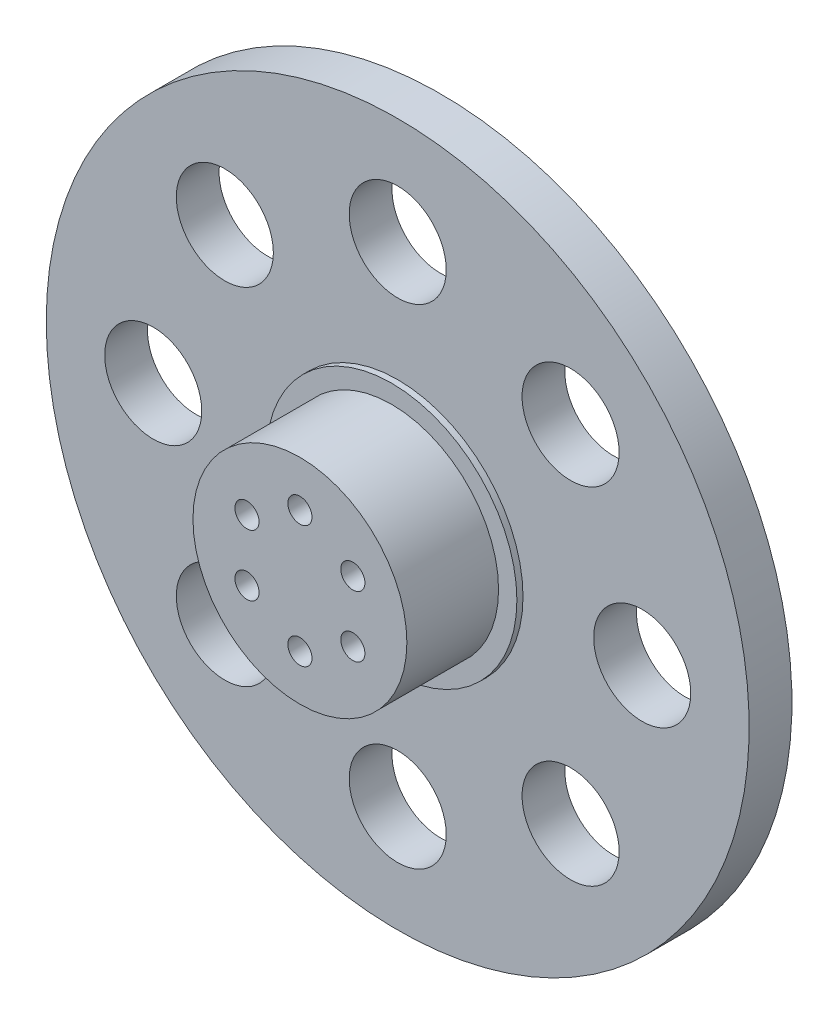
SolidWorks part; units mm, degrees
ref_plane "Front Plane" through (0, 0, 0) normal (0, 0, 1) x (1, 0, 0)
ref_plane "Top Plane" through (0, 0, 0) normal (0, 1, 0) x (1, 0, 0)
ref_plane "Right Plane" through (0, 0, 0) normal (1, 0, 0) x (0, 0, -1)
sketch "Sketch1" plane through (0, 0, 0) normal (0, 0, 1) x (1, 0, 0)
  circle A0 centre (0, 0) radius 17.5
  dimension "D1" = 35
extrude "Boss-Extrude1" add sketch "Sketch1" along normal blind 15
sketch "Sketch7" plane through (0, 0, 0) normal (0, 0, -1) x (-1, 0, 0)
  circle A0 centre (0, 0) radius 20.5
  dimension "D1" = 41
extrude "Boss-Extrude3" add sketch "Sketch7" along normal blind 1
sketch "Sketch3" plane through (0, 0, -1) normal (0, 0, -1) x (-1, 0, 0)
  circle A0 centre (0, 0) radius 57.5
  dimension "D1" = 115
extrude "Boss-Extrude2" add sketch "Sketch3" along normal blind 7
sketch "Sketch4" plane through (0, 0, -8) normal (0, 0, -1) x (-1, 0, 0)
  circle A0 centre (0, 0) radius 11
  dimension "D1" = 22
extrude "Cut-Extrude1" cut sketch "Sketch4" against normal blind 7
sketch "Sketch5" plane through (0, 0, -1) normal (0, 0, -1) x (-1, 0, 0)
  circle A0 centre (0, 0) radius 7.5
  dimension "D1" = 15
extrude "Cut-Extrude2" cut sketch "Sketch5" against normal blind 0.5
sketch "Sketch6" plane through (0, 0, 15) normal (0, 0, 1) x (1, 0, 0)
  circle A0 centre (0, 10) radius 1.975
  dimension "D1" = 3.95
  dimension "D2" = 10
extrude "Cut-Extrude3" cut sketch "Sketch6" against normal blind 6
pattern_circular "CirPattern1" count 6 over 360 about axis through (0, 0, 15) along (0, 0, 1) of "Cut-Extrude3"
sketch "Sketch8" plane through (0, 0, -1) normal (0, 0, 1) x (1, 0, 0)
  circle A0 centre (0, 0) radius 40 construction
  circle A1 centre (-40, 0) radius 7.94
  circle A2 centre (-28.2843, 28.2843) radius 7.94
  circle A3 centre (0, 40) radius 7.94
  circle A4 centre (28.2843, 28.2843) radius 7.94
  circle A5 centre (40, 0) radius 7.94
  circle A6 centre (28.2843, -28.2843) radius 7.94
  circle A7 centre (0, -40) radius 7.94
  circle A8 centre (-28.2843, -28.2843) radius 7.94
  dimension "D1" = 80
  dimension "D2" = 15.88
  dimension "D3" = 8
extrude "Cut-Extrude4" cut sketch "Sketch8" against normal through all
equation "\"N\"= 21"
equation "\"R\"= 65mm"
equation "\"E\" = \"R\" / \"N\" * 0.7"
equation "\"R_r\" = ( 1in / 2 ) / 2"
equation "\"D_p\" = 8cm"
equation "\"D1@Sketch8\"=\"D_p\""
equation "\"N_p\"= 8"
equation "\"D3@Sketch8\"=\"N_p\""
